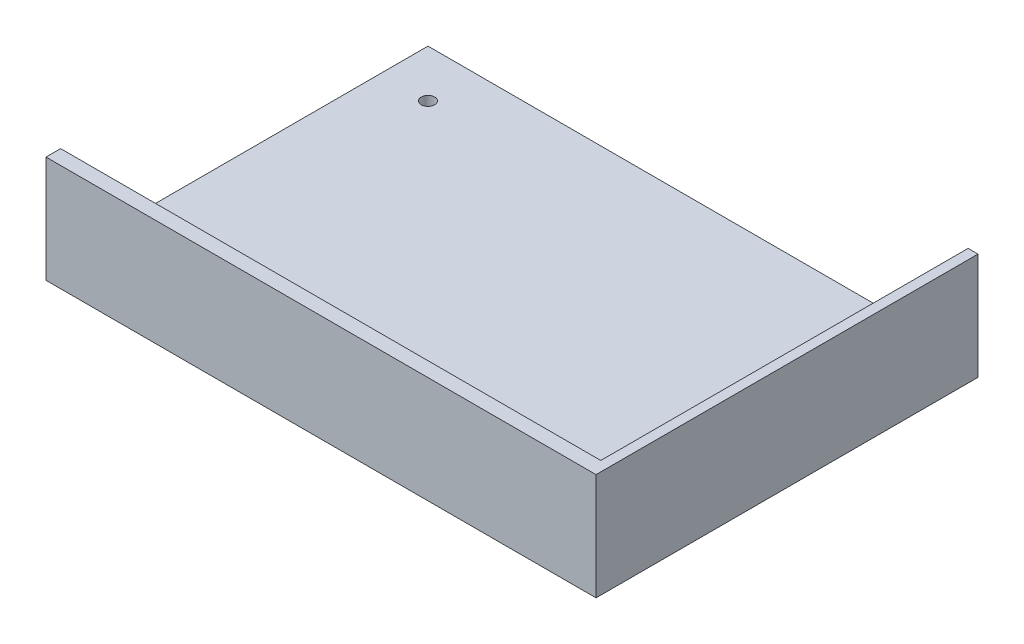
SolidWorks part; units mm, degrees
ref_plane "Front Plane" through (0, 0, 0) normal (0, 0, 1) x (1, 0, 0)
ref_plane "Top Plane" through (0, 0, 0) normal (0, 1, 0) x (1, 0, 0)
ref_plane "Right Plane" through (0, 0, 0) normal (1, 0, 0) x (0, 0, -1)
sketch "Sketch1" plane through (0, 0, 0) normal (0, 1, 0) x (1, 0, 0)
  line L1 (-139.1, -96.6) -> (139.1, -96.6)
  line L2 (-139.1, -96.6) -> (-139.1, 96.6)
  line L3 (-139.1, 96.6) -> (139.1, 96.6)
  line L4 (139.1, -96.6) -> (139.1, 96.6)
  line L5 (-139.1, -96.6) -> (139.1, 96.6) construction
  line L6 (-139.1, 96.6) -> (139.1, -96.6) construction
  point P0 (0, 0)
  dimension "D1" = 278.2
  dimension "D2" = 193.2
extrude "Shell Block" add sketch "Sketch1" along normal blind 27
ref_plane "Shell Front" through (0, 27, 0) normal (0, 1, 0) x (1, 0, 0)
sketch "Sketch2" plane through (0, 27, 0) normal (0, 1, 0) x (1, 0, 0)
  line L1 (-136.6, -92.9) -> (136.6, -92.9)
  line L2 (-136.6, -92.9) -> (-136.6, 92.9)
  line L3 (-136.6, 92.9) -> (136.6, 92.9)
  line L4 (136.6, -92.9) -> (136.6, 92.9)
  line L5 (-136.6, -92.9) -> (136.6, 92.9) construction
  line L6 (-136.6, 92.9) -> (136.6, -92.9) construction
  point P0 (0, 0)
  dimension "D1" = 273.2
  dimension "D2" = 185.8
extrude "Front Opening" cut sketch "Sketch2" against normal blind 1.5
ref_plane "Under Lip" through (0, 25.5, 0) normal (0, 1, 0) x (1, 0, 0)
sketch "Sketch3" plane through (0, 25.5, 0) normal (0, 1, 0) x (1, 0, 0)
  line L1 (-136.6, -94.1) -> (136.6, -94.1)
  line L2 (-136.6, -94.1) -> (-136.6, 94.1)
  line L3 (-136.6, 94.1) -> (136.6, 94.1)
  line L4 (136.6, -94.1) -> (136.6, 94.1)
  line L5 (-136.6, -94.1) -> (136.6, 94.1) construction
  line L6 (-136.6, 94.1) -> (136.6, -94.1) construction
  point P0 (0, 0)
  dimension "D1" = 273.2
  dimension "D2" = 188.2
extrude "Display Pocket" cut sketch "Sketch3" against normal blind 22.5
ref_plane "Back Inner" through (0, 3, 0) normal (0, 1, 0) x (1, 0, 0)
sketch "Sketch4" plane through (0, 3, 0) normal (0, 1, 0) x (1, 0, 0)
  line L1 (-69, 28) -> (-66, 28)
  line L2 (-69, 28) -> (-69, 84)
  line L3 (-69, 84) -> (-66, 84)
  line L4 (-66, 28) -> (-66, 84)
  line L6 (-69, -84) -> (-66, -84)
  line L7 (-69, -84) -> (-69, -28)
  line L8 (-69, -28) -> (-66, -28)
  line L9 (-66, -84) -> (-66, -28)
  line L11 (-77, 28) -> (-74, 28)
  line L12 (-77, 28) -> (-77, 84)
  line L13 (-77, 84) -> (-74, 84)
  line L14 (-74, 28) -> (-74, 84)
  line L16 (-77, -84) -> (-74, -84)
  line L17 (-77, -84) -> (-77, -28)
  line L18 (-77, -28) -> (-74, -28)
  line L19 (-74, -84) -> (-74, -28)
  line L21 (-85, 28) -> (-82, 28)
  line L22 (-85, 28) -> (-85, 84)
  line L23 (-85, 84) -> (-82, 84)
  line L24 (-82, 28) -> (-82, 84)
  line L26 (-85, -84) -> (-82, -84)
  line L27 (-85, -84) -> (-85, -28)
  line L28 (-85, -28) -> (-82, -28)
  line L29 (-82, -84) -> (-82, -28)
  line L31 (-93, 28) -> (-90, 28)
  line L32 (-93, 28) -> (-93, 84)
  line L33 (-93, 84) -> (-90, 84)
  line L34 (-90, 28) -> (-90, 84)
  line L36 (-93, -84) -> (-90, -84)
  line L37 (-93, -84) -> (-93, -28)
  line L38 (-93, -28) -> (-90, -28)
  line L39 (-90, -84) -> (-90, -28)
  line L41 (-101, 28) -> (-98, 28)
  line L42 (-101, 28) -> (-101, 84)
  line L43 (-101, 84) -> (-98, 84)
  line L44 (-98, 28) -> (-98, 84)
  line L46 (-101, -84) -> (-98, -84)
  line L47 (-101, -84) -> (-101, -28)
  line L48 (-101, -28) -> (-98, -28)
  line L49 (-98, -84) -> (-98, -28)
  line L51 (-109, 28) -> (-106, 28)
  line L52 (-109, 28) -> (-109, 84)
  line L53 (-109, 84) -> (-106, 84)
  line L54 (-106, 28) -> (-106, 84)
  line L56 (-109, -84) -> (-106, -84)
  line L57 (-109, -84) -> (-109, -28)
  line L58 (-109, -28) -> (-106, -28)
  line L59 (-106, -84) -> (-106, -28)
  line L61 (-117, 28) -> (-114, 28)
  line L62 (-117, 28) -> (-117, 84)
  line L63 (-117, 84) -> (-114, 84)
  line L64 (-114, 28) -> (-114, 84)
  line L66 (-117, -84) -> (-114, -84)
  line L67 (-117, -84) -> (-117, -28)
  line L68 (-117, -28) -> (-114, -28)
  line L69 (-114, -84) -> (-114, -28)
  line L71 (-125, 28) -> (-122, 28)
  line L72 (-125, 28) -> (-125, 84)
  line L73 (-125, 84) -> (-122, 84)
  line L74 (-122, 28) -> (-122, 84)
  line L76 (-125, -84) -> (-122, -84)
  line L77 (-125, -84) -> (-125, -28)
  line L78 (-125, -28) -> (-122, -28)
  line L79 (-122, -84) -> (-122, -28)
extrude "Vent Slots" cut sketch "Sketch4" against normal blind 4
sketch "Sketch5" plane through (0, 0, 0) normal (1, 0, 0) x (0, 0, -1)
  line L1 (-29, 5) -> (29, 5)
  line L2 (-29, 5) -> (-29, 21)
  line L3 (-29, 21) -> (29, 21)
  line L4 (29, 5) -> (29, 21)
extrude "Cable Exit (-X short side)" cut sketch "Sketch5" against normal blind 140.1
sketch "Sketch6" plane through (0, 3, 0) normal (0, 1, 0) x (1, 0, 0)
  circle A0 centre (-40, 18) radius 1.7
  circle A1 centre (-40, 88) radius 1.7
  circle A2 centre (40, 18) radius 1.7
  circle A3 centre (40, 88) radius 1.7
  circle A4 centre (-52, 40) radius 1.7
  circle A5 centre (-52, 66) radius 1.7
  circle A6 centre (52, 40) radius 1.7
  circle A7 centre (52, 66) radius 1.7
  circle A8 centre (-12, -82) radius 1.7
  circle A9 centre (12, -82) radius 1.7
  circle A10 centre (124, -12) radius 1.7
  circle A11 centre (124, 12) radius 1.7
  circle A12 centre (-12, -12) radius 1.7
  circle A13 centre (-12, 12) radius 1.7
  circle A14 centre (12, -12) radius 1.7
  circle A15 centre (12, 12) radius 1.7
  circle A16 centre (-110, 12) radius 1.7
  circle A17 centre (-110, -12) radius 1.7
  circle A18 centre (-86, 12) radius 1.7
  circle A19 centre (-86, -12) radius 1.7
extrude "Bolt Holes" cut sketch "Sketch6" against normal blind 4
sketch "Sketch7" plane through (0, 0, 0) normal (0, 1, 0) x (1, 0, 0)
  line L1 (-200, -200) -> (0, -200)
  line L2 (-200, -200) -> (-200, 200)
  line L3 (-200, 200) -> (0, 200)
  line L4 (0, -200) -> (0, 200)
extrude "Keep one half (X)" cut sketch "Sketch7" against normal through all and the other way through all
sketch "Sketch8" plane through (0, 0, 0) normal (0, 1, 0) x (1, 0, 0)
  line L1 (-200, 0) -> (200, 0)
  line L2 (-200, 0) -> (-200, 200)
  line L3 (-200, 200) -> (200, 200)
  line L4 (200, 0) -> (200, 200)
extrude "Keep one quarter (Z)" cut sketch "Sketch8" against normal through all and the other way through all
equation "\"DispL\"= 272.0"
equation "\"DispW\"= 187.0"
equation "\"DispT\"= 20.0"
equation "\"Clr\"= 0.6"
equation "\"Wall\"= 2.5"
equation "\"BackT\"= 3.0"
equation "\"CableRoom\"= 4.0"
equation "\"LipW\"= 1.2"
equation "\"LipT\"= 1.5"
equation "\"CableW\"= 58.0"
equation "\"CableH\"= 16.0"
equation "\"BoltD\"= 3.4"
equation "\"ShellL\"= \"DispL\" + 2 * \"Clr\" + 2 * \"Wall\""
equation "\"ShellW\"= \"DispW\" + 2 * \"Clr\" + 2 * \"Wall\""
equation "\"ShellH\"= \"BackT\" + \"DispT\" + \"CableRoom\""
equation "\"D1@Sketch1\" = \"ShellL\""
equation "\"D2@Sketch1\" = \"ShellW\""
equation "\"D1@Shell Block\" = \"ShellH\""
equation "\"D1@Shell Front\" = \"ShellH\""
equation "\"D1@Sketch2\" = \"DispL\" + 2 * \"Clr\""
equation "\"D2@Sketch2\" = \"DispW\" + 2 * \"Clr\" - 2 * \"LipW\""
equation "\"D1@Front Opening\" = \"LipT\""
equation "\"D1@Under Lip\" = \"ShellH\" - \"LipT\""
equation "\"D1@Sketch3\" = \"DispL\" + 2 * \"Clr\""
equation "\"D2@Sketch3\" = \"DispW\" + 2 * \"Clr\""
equation "\"D1@Display Pocket\" = \"ShellH\" - \"LipT\" - \"BackT\""
equation "\"D1@Back Inner\" = \"BackT\""
